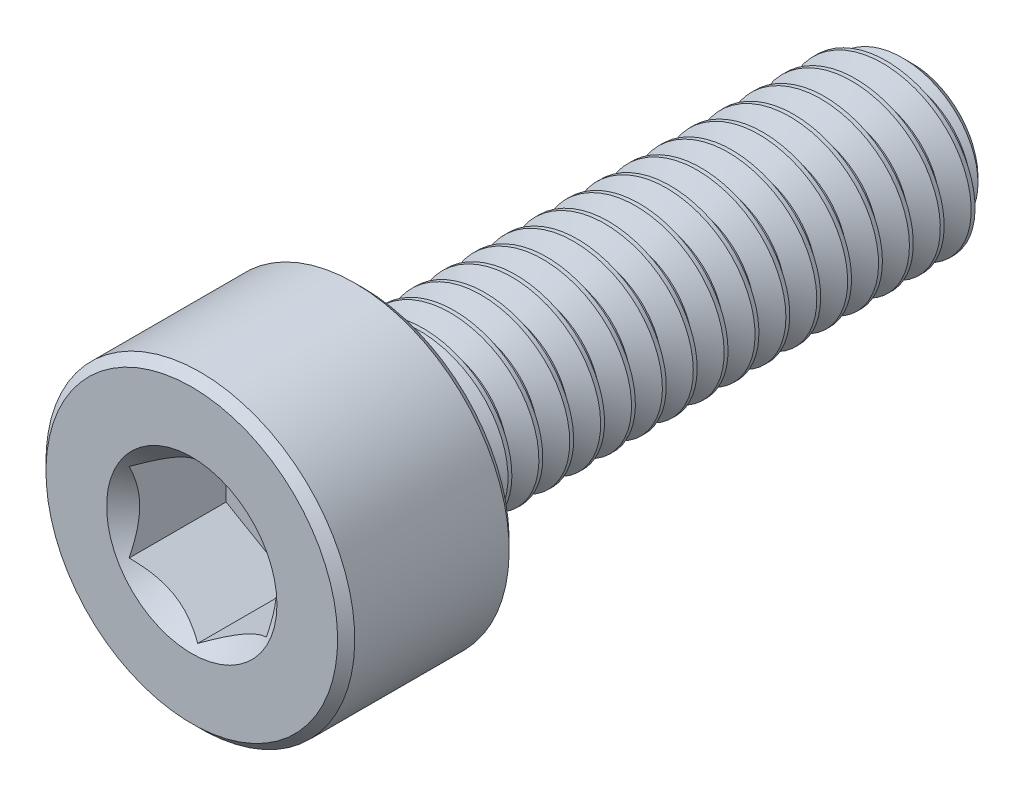
SolidWorks part; units mm, degrees
ref_plane "Front Plane" through (0, 0, 0) normal (0, 0, 1) x (1, 0, 0)
ref_plane "Top Plane" through (0, 0, 0) normal (0, 1, 0) x (1, 0, 0)
ref_plane "Right Plane" through (0, 0, 0) normal (1, 0, 0) x (0, 0, -1)
sketch "Sketch1" plane through (0, 0, 0) normal (1, 0, 0) x (0, 0, -1)
  line L0 (-5.25, 0) -> (5.25, 0) construction
  line L1 (5.25, 0) -> (5.25, 0.9577) construction
  line L2 (5.25, 0.9577) -> (4.9577, 1.25) construction
  line L3 (4.9577, 1.25) -> (4.9125, 1.25) construction
  line L4 (4.9125, 1.25) -> (-2.75, 1.25) construction
  line L5 (-2.75, 1.25) -> (-2.75, 2.25) construction
  line L6 (-2.75, 2.25) -> (-5.25, 2.25) construction
  line L7 (-5.25, 2.25) -> (-5.25, 0) construction
  line L8 (5.25, 0.9577) -> (5.25, 1.25) construction
  line L9 (5.2219, 1.2987) -> (5.4469, 0.909) construction
  line L10 (5.4469, 0.909) -> (5.6719, 1.2987) construction
  line L11 (5.6719, 1.2987) -> (5.2219, 1.2987) construction
  line L12 (5.4469, 1.2987) -> (5.4469, 1.25) construction
  line L13 (5.4469, 0.909) -> (5.4469, 0.9577) construction
  line L14 (5.4187, 0.9577) -> (5.475, 0.9577) construction
  line L15 (5.25, 1.25) -> (5.6437, 1.25) construction
  line L16 (5.2359, 1.2744) -> (5.6578, 1.2744) construction
  line L17 (5.25, 0) -> (5.25, -1.25) construction
  line L18 (-2.875, 2.25) -> (-2.75, 2.125) construction
  line L19 (-5.125, 2.25) -> (-5.25, 2.125) construction
  line L20 (-2.75, 1.25) -> (-2.75, 0) construction
  line L21 (-2.75, 0.625) -> (-0.0833, 0.625) construction
  line L22 (-0.0833, 0.625) -> (2.5833, 0.625) construction
  line L23 (2.5833, 0.625) -> (5.25, 0.625) construction
  line L24 (-0.0833, 0.625) -> (-0.0833, 1.25) construction
  line L25 (-0.0833, 1.25) -> (-0.0833, 2.25) construction
  line L26 (2.5833, 0.625) -> (2.5833, 2.25) construction
  point P0 (-5.25, 1)
  point P3 (4.125, 1.25)
  point P4 (0, 0)
  point P18 (2.5833, 1.25)
  point P22 (5.4469, 0.9577)
  point P24 (4.9125, 1.25)
  point P25 (5.4469, 1.25)
  point P28 (5.4469, 1.2744)
  point P29 (4.125, -1.25)
  point P30 (-0.0833, 1.25)
  point P31 (-4, 2.25)
  point P37 (-3.1875, 2.25)
  point P38 (-5.0625, 2.25)
  point P45 (-0.0833, 0.625)
  point P46 (2.5833, 0.625)
  dimension "D2" = 0.0563
  dimension "D7" = 0.125
  dimension "D8" = 0.125
  dimension "D9" = 0.125
  dimension "D10" = 0.0625
  dimension "D11" = 0.3125
  dimension "Drive Size" = 2
  dimension "Head Diameter" = 4.5
  dimension "Head Height" = 2.5
  dimension "Thread Pitch" = 0.45
  dimension "Thread Dia" = 2.5
  dimension "Length" = 8
  dimension "D12" = 0.3375
  dimension "D4" = 1.125
  dimension "D3" = 45
sketch "Sketch2" plane through (0, 0, 0) normal (1, 0, 0) x (0, 0, -1)
  line L0 (-5.25, 0) -> (-5.25, 2.125)
  line L1 (-5.125, 2.25) -> (-2.875, 2.25)
  line L2 (-2.75, 2.125) -> (-2.75, 1.375)
  line L4 (4.9577, 1.25) -> (5.25, 0.9577)
  line L5 (5.25, 0.9577) -> (5.25, 0)
  line L6 (-2.75, 2.25) -> (-5.25, 2.25) construction
  line L7 (5.25, 0) -> (-5.25, 0)
  line L8 (-5.125, 2.25) -> (-5.25, 2.125) construction
  line L10 (-5.125, 2.25) -> (-5.25, 2.125)
  line L14 (-2.875, 2.25) -> (-2.75, 2.125) construction
  line L16 (-2.875, 2.25) -> (-2.75, 2.125)
  line L17 (-2.75, 1.25) -> (-2.75, 2.25) construction
  line L19 (-2.625, 1.25) -> (4.9577, 1.25)
  line L20 (4.9125, 1.25) -> (-2.75, 1.25) construction
  arc A1 (-2.75, 1.375) -> (-2.625, 1.25) centre (-2.625, 1.375) ccw
  dimension "D3" = 0.125
revolve "Revolve1" add sketch "Sketch2" angle 360 about L7
sketch "Sketch3" plane through (0, 0, 5.25) normal (0, 0, 1) x (1, 0, 0)
  line L1 (1, -0.5774) -> (1, 0.5774)
  line L2 (1, 0.5774) -> (0, 1.1547)
  line L3 (0, 1.1547) -> (-1, 0.5774)
  line L4 (-1, 0.5774) -> (-1, -0.5774)
  line L5 (-1, -0.5774) -> (0, -1.1547)
  line L6 (0, -1.1547) -> (1, -0.5774)
  circle A0 centre (0, 0) radius 1 construction
  circle A1 centre (0, 0) radius 2.25 construction
  circle A2 centre (0, 0) radius 2.25 construction
  circle A3 centre (0, 0) radius 1.1547 construction
  point P13 (0, 0)
  dimension "D1" = 2.3094
extrude "Cut-Extrude1" cut sketch "Sketch3" against normal offset from surface (1.5 mm away) 1 up to face at (0, 2.125, 2.75)
sketch "Sketch4" plane through (0, 0, 5.25) normal (0, 0, 1) x (1, 0, 0)
  circle A0 centre (0, 0) radius 1.2413
  dimension "D1" = 2.4826
extrude "Cut-Extrude2" cut sketch "Sketch4" against normal up to vertex (1.25 mm away) draft 45 up to point (0, 2.25, 4)
sketch "Sketch11" plane through (0, 0, 0) normal (1, 0, 0) x (0, 0, -1)
  line L0 (-5.25, 0) -> (5.25, 0) construction
  line L1 (-5.25, 0) -> (5.25, 0) construction
  line L2 (-1.25, 0) -> (-1.25, 1.25) construction
  line L3 (4.9125, 1.25) -> (-2.75, 1.25) construction
  line L4 (3.75, 0) -> (3.75, 1.25) construction
  line L6 (5.25, 0.9577) -> (5.25, 1.25) construction
  point P2 (-1.25, 0)
  point P3 (3.75, 0)
  dimension "D1" = 1.5
  dimension "D2" = 1.5
sketch "Sketch6" plane through (0, 0, -5.25) normal (0, 0, -1) x (-1, 0, 0)
  circle A0 centre (0, 0) radius 1.25
curve "Helix/Spiral1" pitch 0.45 height 8.45 turns 18.7778
sketch "Sketch10" plane through (0, 0, 0) normal (1, 0, 0) x (0, 0, -1)
  line L0 (-2.625, -2.25) -> (-2.625, 2.25)
  line L5 (-5.25, 0) -> (5.25, 0) construction
  line L6 (-2.625, 1.25) -> (-2.625, -1.25) construction
  point P3 (-2.625, 0)
split "Split1" trim tools "Sketch10" bodies to split 106 resulting bodies 114 115
sketch "Sketch7" plane through (0, 0, 0) normal (1, 0, 0) x (0, 0, -1)
  line L0 (5.2359, 1.2744) -> (5.6578, 1.2744)
  line L1 (5.6578, 1.2744) -> (5.475, 0.9577)
  line L2 (5.475, 0.9577) -> (5.4187, 0.9577)
  line L3 (5.4187, 0.9577) -> (5.2359, 1.2744)
sweep "Cut-Sweep1" cut profiles "Sketch7" path "Helix/Spiral1" align with end faces yes
sketch "Sketch8" plane through (0, 0, 0) normal (1, 0, 0) x (0, 0, -1)
  line L0 (-2.75, 0) -> (-2.75, 1.25)
  line L1 (-2.625, -1.25) -> (-2.625, 1.25) construction
  line L2 (-2.75, 1.25) -> (-2.625, 1.25)
  line L4 (-2.625, 1.25) -> (-1.9033, 0)
  line L5 (-1.9033, 0) -> (-2.75, 0)
  line L6 (4.9125, 1.25) -> (-2.75, 1.25) construction
  line L7 (-5.25, 0) -> (5.25, 0) construction
  dimension "D1" = 60
revolve "Revolve2" add sketch "Sketch8" angle 360 about L5
equation "\"D2@Sketch1\" = \"Thread Pitch@Sketch1\" / 8"
equation "\"D4@Helix/Spiral1\" = \"Thread Pitch@Sketch1\""
equation "\"D7@Sketch1\" = \"Head Height@Sketch1\" * .05"
equation "\"D8@Sketch1\"=\"D7@Sketch1\""
equation "\"D9@Sketch1\"=\"D7@Sketch1\""
equation "\"D10@Sketch1\"=\"D7@Sketch1\"/2"
equation "\"D11@Sketch1\"=\"D10@Sketch1\"*5"
equation "\"D4@Sketch1\"=\"Thread Pitch@Sketch1\"*2.5"
equation "\"D12@Sketch1\"=\"Thread Pitch@Sketch1\"*.75"
equation "\"D3@Helix/Spiral1\"=\"Length@Sketch1\"+\"Thread Pitch@Sketch1\""
equation "\"D3@Sketch2\"=\"Thread Dia@Sketch1\"*0.05"
equation "\"D1@Sketch11\"=\"Length@Sketch1\"*0.1875"
equation "\"D2@Sketch11\"=\"D1@Sketch11\""
equation "\"D1@Sketch4\"=\"D1@Sketch3\"*1.075"
